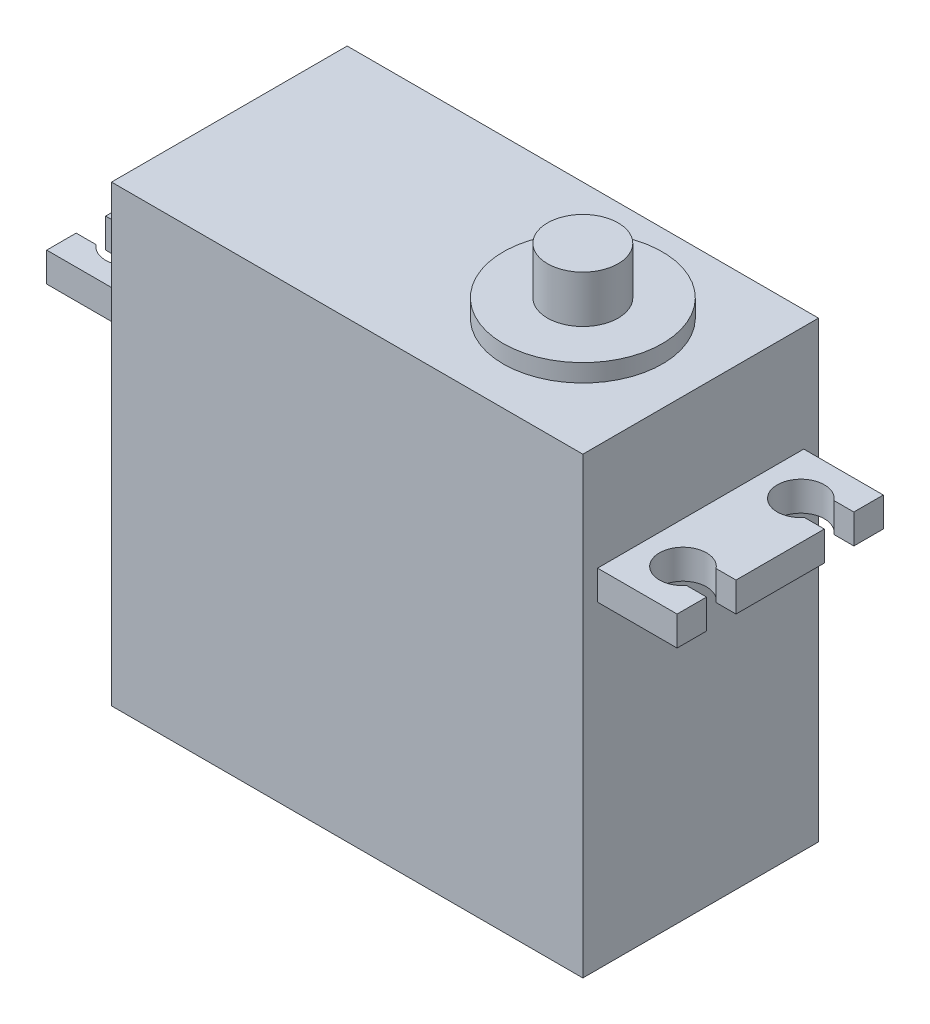
SolidWorks part; units mm, degrees
ref_plane "Front" through (0, 0, 0) normal (0, 0, 1) x (1, 0, 0)
ref_plane "Top" through (0, 0, 0) normal (0, 1, 0) x (1, 0, 0)
ref_plane "Right" through (0, 0, 0) normal (1, 0, 0) x (0, 0, -1)
sketch "Эскиз1" plane through (0, 0, 0) normal (0, 1, 0) x (1, 0, 0)
  line L0 (0, -10) -> (0, 10) construction
  line L1 (-20, 10) -> (20, 10)
  line L2 (-20, 10) -> (-20, -10)
  line L3 (-20, -10) -> (20, -10)
  line L4 (20, 10) -> (20, -10)
  line L5 (-20, 10) -> (20, -10) construction
  line L6 (-20, -10) -> (20, 10) construction
  line L7 (-20, 0) -> (20, 0) construction
  line L8 (20, 8.75) -> (26.75, 8.75)
  line L9 (20, 8.75) -> (20, -8.75)
  line L10 (20, -8.75) -> (26.75, -8.75)
  line L11 (26.75, 8.75) -> (26.75, -8.75)
  line L12 (-23.5, -5) -> (-26.75, -5) construction
  line L13 (-20, 8.75) -> (-26.75, 8.75)
  line L14 (-20, 8.75) -> (-20, -8.75)
  line L15 (-20, -8.75) -> (-26.75, -8.75)
  line L16 (-26.75, 8.75) -> (-26.75, -8.75)
  line L17 (-23.5, 3.75) -> (-26.75, 3.75)
  line L18 (-23.5, 3.75) -> (-23.5, 6.25)
  line L19 (-23.5, 6.25) -> (-26.75, 6.25)
  line L20 (-26.75, 3.75) -> (-26.75, 6.25)
  line L21 (23.5, 3.75) -> (26.75, 3.75)
  line L22 (23.5, 3.75) -> (23.5, 6.25)
  line L23 (23.5, 6.25) -> (26.75, 6.25)
  line L24 (26.75, 3.75) -> (26.75, 6.25)
  line L25 (23.5, -6.25) -> (26.75, -6.25)
  line L26 (23.5, -6.25) -> (23.5, -3.75)
  line L27 (23.5, -3.75) -> (26.75, -3.75)
  line L28 (26.75, -6.25) -> (26.75, -3.75)
  line L29 (-23.5, -6.25) -> (-26.75, -6.25)
  line L30 (-23.5, -6.25) -> (-23.5, -3.75)
  line L31 (-23.5, -3.75) -> (-26.75, -3.75)
  line L32 (-26.75, -6.25) -> (-26.75, -3.75)
  line L33 (-23.5, 5) -> (-26.75, 5) construction
  line L34 (23.5, 5) -> (26.75, 5) construction
  line L35 (23.5, -5) -> (26.75, -5) construction
  circle A0 centre (-23.5, 5) radius 2
  circle A1 centre (-23.5, -5) radius 2
  circle A2 centre (23.5, 5) radius 2
  circle A3 centre (23.5, -5) radius 2
  point P0 (0, 0)
  dimension "D5" = 4
  dimension "D1" = 40
  dimension "D2" = 20
  dimension "D3" = 53.5
  dimension "D4" = 17.5
  dimension "D6" = 47
  dimension "D7" = 10
  dimension "D8" = 2.5
extrude "Бобышка-Вытянуть1" add sketch "Эскиз1" along normal blind 2.5 contours A1 L29 L16 L15 L2 L13 L19 A0 L17 L31 | A3 L27 L11 L21 A2 L23 L8 L4 L10 L25 region at (-23.1226, 0, 0) region at (23.1226, 0, 0)
extrude "Бобышка-Вытянуть4" add sketch "Эскиз1<7>" against normal blind 27 separate body contours L4 L1 L2 L3 region at (0, 0, 0)
sketch "Эскиз1<7>" plane through (0, 0, 0) normal (0, 1, 0) x (1, 0, 0) same geometry as "Эскиз1"
extrude "Бобышка-Вытянуть5" add sketch "Эскиз1<8>" along normal blind 11.5 contours L4 L1 L2 L3 region at (0, 0, 0)
sketch "Эскиз1<8>" plane through (0, 0, 0) normal (0, 1, 0) x (1, 0, 0) same geometry as "Эскиз1"
sketch "Эскиз2" plane through (0, 11.5, 0) normal (0, 1, 0) x (1, 0, 0)
  line L0 (-20, 0) -> (20, 0) construction
  line L1 (-20, 10) -> (-20, -10) construction
  line L2 (20, 8.75) -> (20, -8.75) construction
  circle A0 centre (10, 0) radius 6.75
  circle A1 centre (10, 0) radius 3
  dimension "D1" = 13.5
  dimension "D2" = 6
  dimension "D3" = 30
extrude "Бобышка-Вытянуть6" add sketch "Эскиз2" along normal blind 5.5 contours A1 L0 | L0 A1 region at (10, 11.5, 1.2732) region at (10, 11.5, -1.2732)
extrude "Бобышка-Вытянуть7" add sketch "Эскиз2<3>" along normal blind 1.5
sketch "Эскиз2<3>" plane through (0, 11.5, 0) normal (0, 1, 0) x (1, 0, 0) same geometry as "Эскиз2"
